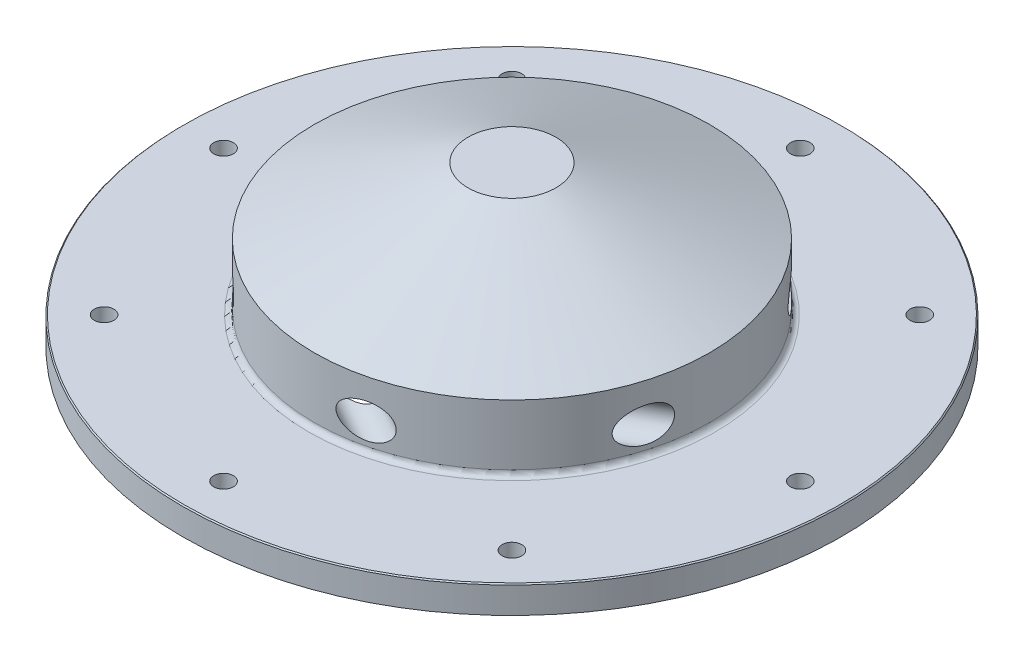
SolidWorks part; units mm, degrees
material "7075-T6 (SN)"
ref_plane "Front Plane" through (0, 0, 0) normal (0, 0, 1) x (1, 0, 0)
ref_plane "Top Plane" through (0, 0, 0) normal (0, 1, 0) x (1, 0, 0)
ref_plane "Right Plane" through (0, 0, 0) normal (1, 0, 0) x (0, 0, -1)
sketch "Sketch2" plane through (0, 0, 0) normal (0, 1, 0) x (1, 0, 0)
  circle A0 centre (0, 0) radius 38.1
  dimension "D1" = 76.2
extrude "Boss-Extrude1" add sketch "Sketch2" along normal blind 3.175
hole_wizard "Tap Drill for #4-40 Tap1" positions "Sketch3" profile "Sketch4" hole size "#4-40" standard "ANSI Inch" end condition through all
sketch "Sketch3" plane through (0, 0, 0) normal (0, -1, 0) x (-1, 0, 0)
  point P0 (0, -33.3375)
  dimension "D1" = 33.3375
sketch "Sketch4" plane through (0, 0, 33.3375) normal (1, 0, 0) x (0, 0, -1)
  line L0 (0, 0) -> (0, 3.175)
  line L1 (0, 3.175) -> (1.1303, 3.175)
  line L2 (1.1303, 3.175) -> (1.1303, 0)
  line L5 (1.1303, 0) -> (0, 0)
  line L11 (0, -6.35) -> (0, 107.95) construction
  dimension "Thru Hole Dia." = 2.2606
  dimension "Thru Hole Depth" = 3.175
pattern_circular "CirPattern1" count 8 over 360 about axis through (0, 0, 0) along (0, 1, 0) of "Tap Drill for #4-40 Tap1"
sketch "Sketch5" plane through (0, 3.175, 0) normal (0, 1, 0) x (1, 0, 0)
  circle A0 centre (0, 0) radius 28.575
  dimension "D1" = 57.15
sketch "Sketch7" plane through (0, 3.175, 0) normal (0, 1, 0) x (1, 0, 0)
  circle A0 centre (0, 0) radius 22.86
  dimension "D1" = 45.72
extrude "Boss-Extrude2" add sketch "Sketch7" along normal blind 7.62
sketch "Sketch8" plane through (0, 0, 0) normal (0, -1, 0) x (1, 0, 0)
  circle A0 centre (0, 0) radius 19.05
  dimension "D1" = 38.1
extrude "Cut-Extrude1" cut sketch "Sketch8" against normal blind 8.89
hole_wizard "5/32 (0.15625) Diameter Hole1" positions "Sketch11" profile "Sketch12" hole size "5/32" standard "ANSI Inch" end condition through all
sketch "Sketch11" plane through (0, 0, 0) normal (0, 0, 1) x (1, 0, 0)
  line L0 (0, -5.9373) -> (0, 5.9373) construction
  line L1 (22.86, 3.175) -> (-22.86, 3.175) construction
  point P0 (-16.51, 6.35)
  dimension "D1" = 16.51
  dimension "D2" = 3.175
sketch "Sketch12" plane through (-16.51, 6.35, 0) normal (1, 0, 0) x (0, 1, 0)
  line L0 (0, 0) -> (0, 38.1)
  line L1 (0, 38.1) -> (1.9844, 38.1)
  line L2 (1.9844, 38.1) -> (1.9844, 0)
  line L5 (1.9844, 0) -> (0, 0)
  line L11 (0, -6.35) -> (0, 107.95) construction
  dimension "Thru Hole Dia." = 3.9688
  dimension "Thru Hole Depth" = 38.1
pattern_circular "CirPattern2" count 6 over 360 about axis through (0, 10.795, 0) along (0, 1, 0) of "5/32 (0.15625) Diameter Hole1"
sketch "Sketch13" plane through (0, 10.795, 0) normal (0, 1, 0) x (1, 0, 0)
  circle A0 centre (0, 0) radius 22.86
  circle A1 centre (0, 0) radius 22.86 construction
  dimension "D1" = 0
ref_plane "Plane2" through (0, 18.415, 0) normal (0, 1, 0) x (1, 0, 0)
sketch "Sketch14" plane through (0, 18.415, 0) normal (0, 1, 0) x (1, 0, 0)
  circle A0 centre (0, 0) radius 5.08
  dimension "D1" = 10.16
loft "Loft2" add profiles "Sketch14", "Sketch13" connector at (-0.0647, 18.415, 5.0796) connector at (0, 10.795, 22.86)
fillet "Fillet1" radius 0.635 1 edges at (0, 8.89, -19.05)
chamfer "Chamfer1" distance 0.127 angle 45 1 edges at (0, 3.175, 38.1)
fillet "Fillet2" radius 0.635 1 edges at (0, 3.175, 22.86)
